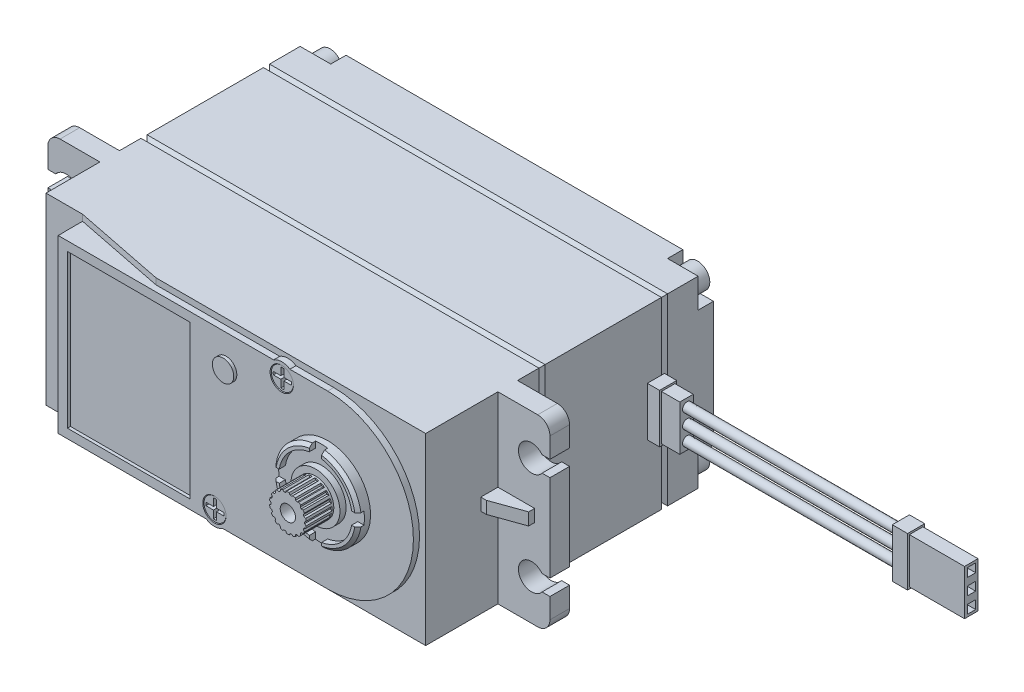
SolidWorks part; units mm, degrees
ref_plane "前视基准面" through (0, 0, 0) normal (0, 0, 1) x (1, 0, 0)
ref_plane "上视基准面" through (0, 0, 0) normal (0, 1, 0) x (1, 0, 0)
ref_plane "右视基准面" through (0, 0, 0) normal (1, 0, 0) x (0, 0, -1)
sketch "草图1" plane through (0, 0, 0) normal (0, 0, 1) x (1, 0, 0)
  line L1 (-32.5, 15) -> (32.5, 15)
  line L2 (-32.5, 15) -> (-32.5, -15)
  line L3 (-32.5, -15) -> (32.5, -15)
  line L4 (32.5, 15) -> (32.5, -15)
  dimension "D1" = 32.5
  dimension "D2" = 65
  dimension "D3" = 15
  dimension "D4" = 30
extrude "凸台-拉伸1" add sketch "草图1" along normal blind 8
chamfer "倒角1" distance 0.5 angle 45 4 edges at (0, 15, 8) (32.5, 0, 8) (0, -15, 8) (-32.5, 0, 8)
sketch "草图2" plane through (0, 0, 8) normal (0, 0, 1) x (1, 0, 0)
  line L0 (32.5, 15) -> (32.5, -15) construction
  line L1 (32.5, -15) -> (-32.5, -15) construction
  line L2 (-32.5, -15) -> (-32.5, 15) construction
  line L3 (-32.5, 15) -> (32.5, 15) construction
  line L4 (32.5, 15) -> (32.5, -15)
  line L5 (32.5, -15) -> (-32.5, -15)
  line L6 (-32.5, -15) -> (-32.5, 15)
  line L7 (-32.5, 15) -> (32.5, 15)
extrude "凸台-拉伸2" add sketch "草图2" along normal blind 20
chamfer "倒角2" distance 0.5 angle 45 4 edges at (32.5, 0, 28) (0, -15, 28) (-32.5, 0, 28) (0, 15, 28)
sketch "草图3" plane through (0, 0, 28) normal (0, 0, 1) x (1, 0, 0)
  line L0 (32.5, 15) -> (32.5, -15) construction
  line L1 (32.5, -15) -> (-32.5, -15) construction
  line L2 (-32.5, -15) -> (-32.5, 15) construction
  line L3 (-32.5, 15) -> (32.5, 15) construction
  line L4 (32.5, 15) -> (32.5, -15)
  line L5 (32.5, -15) -> (-32.5, -15)
  line L6 (-32.5, -15) -> (-32.5, 15)
  line L7 (-32.5, 15) -> (32.5, 15)
extrude "凸台-拉伸3" add sketch "草图3" along normal blind 20
chamfer "倒角3" distance 0.5 angle 45 8 edges at (-32.5, 0, 28) (0, -15, 28) (0, 15, 28) (32.5, 0, 28) (32.5, 0, 8) (0, 15, 8) (-32.5, 0, 8) (0, -15, 8)
sketch "草图4" plane through (0, 0, 48) normal (0, 0, 1) x (1, 0, 0)
  line L0 (32.5, -15) -> (32.5, 15) construction
  circle A0 centre (17.5, 0) radius 7
  dimension "D1" = 15
  dimension "D2" = 14
extrude "凸台-拉伸4" add sketch "草图4" along normal blind 2
sketch "草图5" plane through (0, 0, 50) normal (0, 0, 1) x (1, 0, 0)
  circle A0 centre (17.5, 0) radius 3
  dimension "D1" = 6
extrude "凸台-拉伸5" add sketch "草图5" along normal blind 4.5
sketch "草图6" plane through (0, 0, 54.5) normal (0, 0, 1) x (1, 0, 0)
  circle A0 centre (17.5, 0) radius 1.25
  dimension "D1" = 2.5
extrude "切除-拉伸1" cut sketch "草图6" against normal blind 5
sketch "草图7" plane through (0, 0, 50) normal (0, 0, 1) x (1, 0, 0)
  circle A0 centre (17.5, 0) radius 4
  circle A1 centre (17.5, 0) radius 6
  dimension "D1" = 12
  dimension "D2" = 8
extrude "切除-拉伸2" cut sketch "草图7" against normal blind 1
sketch "草图8" plane through (0, 0, 50) normal (0, 0, 1) x (1, 0, 0)
  line L0 (18.5, -6.9282) -> (18.5, -5.9161)
  line L1 (24.4282, -1) -> (23.4161, -1)
  line L2 (10.5718, -1) -> (11.5839, -1)
  line L3 (18.5, 6.9282) -> (18.5, 5.9161)
  line L4 (16.5, -6.9282) -> (16.5, -5.9161)
  line L5 (24.4282, 1) -> (23.4161, 1)
  line L6 (16.5, 6.9282) -> (16.5, 5.9161)
  line L7 (10.5718, 1) -> (11.5839, 1)
  line L8 (10.5, 0) -> (24.5, 0) construction
  circle A1 centre (17.5, 0) radius 7 construction
  circle A11 centre (17.5, 0) radius 7 construction
  circle A14 centre (17.5, 0) radius 6 construction
  arc A15 (11.5839, 1) -> (11.5839, -1) centre (17.5, 0) ccw
  arc A16 (10.5718, 1) -> (10.5718, -1) centre (17.5, 0) ccw
  arc A17 (18.5, 6.9282) -> (16.5, 6.9282) centre (17.5, 0) ccw
  arc A18 (18.5, 5.9161) -> (16.5, 5.9161) centre (17.5, 0) ccw
  arc A19 (24.4282, -1) -> (24.4282, 1) centre (17.5, 0) ccw
  arc A20 (23.4161, -1) -> (23.4161, 1) centre (17.5, 0) ccw
  arc A21 (16.5, -5.9161) -> (18.5, -5.9161) centre (17.5, 0) ccw
  arc A22 (16.5, -6.9282) -> (18.5, -6.9282) centre (17.5, 0) ccw
  point P12 (21.5, 7)
  point P13 (21.5, -7.2442)
  point P16 (23.5, 7)
  point P17 (23.5, -7.2442)
  point P29 (17.5, 0)
  dimension "D2" = 1
  dimension "D3" = 1
  dimension "D4" = 1
  dimension "D5" = 1
  dimension "D1" = 4
extrude "切除-拉伸3" cut sketch "草图8" against normal blind 1
chamfer "倒角4" distance 0.5 angle 45 4 edges at (22.4497, -4.9497, 50) (22.4497, 4.9497, 50) (12.5503, 4.9497, 50) (12.5503, -4.9497, 50)
sketch "草图9" plane through (0, 0, 54.5) normal (0, 0, 1) x (1, 0, 0)
  line L0 (18.1005, 2.6732) -> (18.3385, 2.8804)
  line L58 (17.15, 2.7174) -> (17.3027, 2.9935)
  line L92 (16.8995, 2.6732) -> (16.6615, 2.8804)
  line L94 (17.85, 2.7174) -> (17.6973, 2.9935)
  line L96 (18.9786, 2.3066) -> (19.2731, 2.42)
  line L98 (18.7583, 2.4338) -> (18.7092, 2.7455)
  line L100 (19.6783, 1.6618) -> (19.9938, 1.6676)
  line L102 (19.5148, 1.8567) -> (19.5753, 2.1664)
  line L104 (20.1153, 0.8166) -> (20.4138, 0.7141)
  line L106 (20.0283, 1.0556) -> (20.1911, 1.3259)
  line L108 (20.2369, -0.1272) -> (20.4823, -0.3256)
  line L110 (20.2369, 0.1272) -> (20.4823, 0.3256)
  line L112 (20.0283, -1.0556) -> (20.1911, -1.3259)
  line L114 (20.1153, -0.8166) -> (20.4138, -0.7141)
  line L116 (19.5148, -1.8567) -> (19.5753, -2.1664)
  line L118 (19.6783, -1.6618) -> (19.9938, -1.6676)
  line L120 (18.7583, -2.4338) -> (18.7092, -2.7455)
  line L122 (18.9786, -2.3066) -> (19.2731, -2.42)
  line L123 (17.85, -2.7174) -> (17.6973, -2.9935)
  line L124 (18.1005, -2.6732) -> (18.3385, -2.8804)
  line L125 (16.8995, -2.6732) -> (16.6615, -2.8804)
  line L126 (17.15, -2.7174) -> (17.3027, -2.9935)
  line L127 (16.0214, -2.3066) -> (15.7269, -2.42)
  line L128 (16.2417, -2.4338) -> (16.2908, -2.7455)
  line L129 (15.3217, -1.6618) -> (15.0062, -1.6676)
  line L130 (15.4852, -1.8567) -> (15.4247, -2.1664)
  line L131 (14.8847, -0.8166) -> (14.5862, -0.7141)
  line L132 (14.9717, -1.0556) -> (14.8089, -1.3259)
  line L133 (14.7631, 0.1272) -> (14.5177, 0.3256)
  line L134 (14.7631, -0.1272) -> (14.5177, -0.3256)
  line L135 (14.9717, 1.0556) -> (14.8089, 1.3259)
  line L136 (14.8847, 0.8166) -> (14.5862, 0.7141)
  line L137 (15.4852, 1.8567) -> (15.4247, 2.1664)
  line L138 (15.3217, 1.6618) -> (15.0062, 1.6676)
  line L139 (16.2417, 2.4338) -> (16.2908, 2.7455)
  line L140 (16.0214, 2.3066) -> (15.7269, 2.42)
  arc A53 (17.15, 2.7174) -> (16.8995, 2.6732) centre (17.5, 0) ccw
  arc A86 (18.3385, 2.8804) -> (17.6973, 2.9935) centre (17.5, 0) ccw
  circle A88 centre (17.5, 0) radius 3 construction
  arc A89 (17.3027, 2.9935) -> (16.6615, 2.8804) centre (17.5, 0) ccw
  arc A90 (18.1005, 2.6732) -> (17.85, 2.7174) centre (17.5, 0) ccw
  arc A91 (19.2731, 2.42) -> (18.7092, 2.7455) centre (17.5, 0) ccw
  arc A92 (18.9786, 2.3066) -> (18.7583, 2.4338) centre (17.5, 0) ccw
  arc A93 (19.9938, 1.6676) -> (19.5753, 2.1664) centre (17.5, 0) ccw
  arc A94 (19.6783, 1.6618) -> (19.5148, 1.8567) centre (17.5, 0) ccw
  arc A95 (20.4138, 0.7141) -> (20.1911, 1.3259) centre (17.5, 0) ccw
  arc A96 (20.1153, 0.8166) -> (20.0283, 1.0556) centre (17.5, 0) ccw
  arc A97 (20.4823, -0.3256) -> (20.4823, 0.3256) centre (17.5, 0) ccw
  arc A98 (20.2369, -0.1272) -> (20.2369, 0.1272) centre (17.5, 0) ccw
  arc A99 (20.1911, -1.3259) -> (20.4138, -0.7141) centre (17.5, 0) ccw
  arc A100 (20.0283, -1.0556) -> (20.1153, -0.8166) centre (17.5, 0) ccw
  arc A101 (19.5753, -2.1664) -> (19.9938, -1.6676) centre (17.5, 0) ccw
  arc A102 (19.5148, -1.8567) -> (19.6783, -1.6618) centre (17.5, 0) ccw
  arc A103 (18.7092, -2.7455) -> (19.2731, -2.42) centre (17.5, 0) ccw
  arc A104 (18.7583, -2.4338) -> (18.9786, -2.3066) centre (17.5, 0) ccw
  arc A105 (17.6973, -2.9935) -> (18.3385, -2.8804) centre (17.5, 0) ccw
  arc A106 (17.85, -2.7174) -> (18.1005, -2.6732) centre (17.5, 0) ccw
  arc A107 (16.6615, -2.8804) -> (17.3027, -2.9935) centre (17.5, 0) ccw
  arc A108 (16.8995, -2.6732) -> (17.15, -2.7174) centre (17.5, 0) ccw
  arc A109 (15.7269, -2.42) -> (16.2908, -2.7455) centre (17.5, 0) ccw
  arc A110 (16.0214, -2.3066) -> (16.2417, -2.4338) centre (17.5, 0) ccw
  arc A111 (15.0062, -1.6676) -> (15.4247, -2.1664) centre (17.5, 0) ccw
  arc A112 (15.3217, -1.6618) -> (15.4852, -1.8567) centre (17.5, 0) ccw
  arc A113 (14.5862, -0.7141) -> (14.8089, -1.3259) centre (17.5, 0) ccw
  arc A114 (14.8847, -0.8166) -> (14.9717, -1.0556) centre (17.5, 0) ccw
  arc A115 (14.5177, 0.3256) -> (14.5177, -0.3256) centre (17.5, 0) ccw
  arc A116 (14.7631, 0.1272) -> (14.7631, -0.1272) centre (17.5, 0) ccw
  arc A117 (14.8089, 1.3259) -> (14.5862, 0.7141) centre (17.5, 0) ccw
  arc A118 (14.9717, 1.0556) -> (14.8847, 0.8166) centre (17.5, 0) ccw
  arc A119 (15.4247, 2.1664) -> (15.0062, 1.6676) centre (17.5, 0) ccw
  arc A120 (15.4852, 1.8567) -> (15.3217, 1.6618) centre (17.5, 0) ccw
  arc A121 (16.2908, 2.7455) -> (15.7269, 2.42) centre (17.5, 0) ccw
  arc A122 (16.2417, 2.4338) -> (16.0214, 2.3066) centre (17.5, 0) ccw
  point P76 (17.5, 0)
extrude "切除-拉伸4" cut sketch "草图9" against normal blind 4.2
ref_plane "基准面1" through (0, 0, 32) normal (0, 0, -1) x (-1, 0, 0)
sketch "草图10" plane through (0, 0, 32) normal (0, 0, -1) x (-1, 0, 0)
  line L2 (41, -9.7) -> (41, -15)
  line L3 (-32.5, -15) -> (-32.5, 15) construction
  line L4 (-41, 15) -> (-41, 9.7)
  line L5 (41, 7.1) -> (41, -7.1)
  line L6 (-32.5, 15) -> (-41, 15)
  line L7 (-32.5, -15) -> (-41, -15)
  line L8 (-32.5, -15) -> (-32.5, 15)
  line L10 (-39.7125, 9.7) -> (-41, 9.7)
  line L11 (-39.7125, 7.1) -> (-41, 7.1)
  line L12 (-39.7125, -7.1) -> (-41, -7.1)
  line L13 (-39.7125, -9.7) -> (-41, -9.7)
  line L14 (-41, 7.1) -> (-41, -7.1)
  line L15 (-41, -9.7) -> (-41, -15)
  line L16 (39.7125, -9.7) -> (41, -9.7)
  line L17 (39.7125, -7.1) -> (41, -7.1)
  line L18 (39.7125, 7.1) -> (41, 7.1)
  line L19 (39.7125, 9.7) -> (41, 9.7)
  line L20 (32.5, -15) -> (32.5, 15)
  line L21 (32.5, -15) -> (41, -15)
  line L22 (32.5, 15) -> (41, 15)
  line L23 (41, 15) -> (41, 9.7)
  arc A0 (-39.7125, 7.1) -> (-39.7125, 9.7) centre (-38, 8.4) ccw
  arc A1 (-39.7125, -7.1) -> (-39.7125, -9.7) centre (-38, -8.4) cw
  arc A2 (39.7125, -7.1) -> (39.7125, -9.7) centre (38, -8.4) ccw
  arc A3 (39.7125, 7.1) -> (39.7125, 9.7) centre (38, 8.4) cw
  point P10 (-41, -23.8015)
  dimension "D4" = 4.3
extrude "凸台-拉伸6" add sketch "草图10" against normal blind 3.2
sketch "草图11" plane through (0, 0, 35.2) normal (0, 0, 1) x (1, 0, 0)
  line L2 (-38.5, -0.4932) -> (-32.5, -0.4932)
  line L3 (-38.5, 1.5068) -> (-32.5, 1.5068)
  line L4 (-32.5, 15) -> (-32.5, -15) construction
  line L5 (-32.5, 1.5068) -> (-32.5, -0.4932)
  line L6 (-38.5, 1.5068) -> (-38.5, -0.4932)
  line L8 (38.5, 1.5068) -> (38.5, -0.4932)
  line L9 (32.5, 1.5068) -> (32.5, -0.4932)
  line L10 (-32.5, 15) -> (-32.5, -15) construction
  line L11 (-38.5, 15) -> (-38.5, -15) construction
  line L12 (38.5, 1.5068) -> (32.5, 1.5068)
  line L13 (38.5, -0.4932) -> (32.5, -0.4932)
  point P4 (-41, -0.4932)
  point P5 (-31.3402, -0.4932)
  point P6 (-41, 1.5068)
  point P7 (-31.3402, 1.5068)
  dimension "D3" = 6
extrude "凸台-拉伸7" add sketch "草图11" along normal blind 2.8
sketch "草图12" plane through (0, -0.4932, 0) normal (0, -1, 0) x (1, 0, 0)
  line L0 (-38.5, 36.1787) -> (-33.4098, 38)
  line L1 (-38.5, 38) -> (-38.5, 35.2) construction
  line L2 (-33.4098, 38) -> (-38.5, 38)
  line L3 (-38.5, 38) -> (-38.5, 36.1787)
  line L6 (38.5, 38) -> (38.5, 36.1787)
  line L7 (33.4098, 38) -> (38.5, 38)
  line L8 (38.5, 36.1787) -> (33.4098, 38)
extrude "切除-拉伸5" cut sketch "草图12" against normal blind 2.8
sketch "草图15" plane through (0, 0, 48) normal (0, 0, 1) x (1, 0, 0)
  line L0 (17.5, 14) -> (-26.5, 14)
  line L1 (17.5, -14) -> (-26.5, -14)
  line L2 (-26.5, 14) -> (-26.5, -14)
  line L3 (-32.5, 15) -> (-32.5, -15) construction
  line L4 (-32.5, 15) -> (32.5, 15)
  line L5 (32.5, 15) -> (32.5, -15)
  line L6 (32.5, -15) -> (-32.5, -15)
  line L7 (-32.5, -15) -> (-32.5, 15)
  arc A1 (17.5, -14) -> (17.5, 14) centre (17.5, 0) ccw
  dimension "D1" = 28
  dimension "D2" = 6
extrude "切除-拉伸6" cut sketch "草图15" against normal blind 1
sketch "草图16" plane through (0, 0, 47) normal (0, 0, 1) x (1, 0, 0)
  line L0 (-32.5, -15) -> (32.5, -15) construction
  line L1 (-32.5, 15) -> (-26.5251, 15)
  line L2 (-32.5, 15) -> (-32.5, -15)
  line L3 (-32.5, -15) -> (-26.5251, -15)
  line L4 (-26.5251, 15) -> (-26.5251, -15)
extrude "切除-拉伸7" cut sketch "草图16" against normal blind 3
sketch "草图17" plane through (0, -15, 0) normal (0, -1, 0) x (1, 0, 0)
  line L0 (-26.5251, 44) -> (-11.5251, 47)
  line L1 (-26.5251, 47) -> (32.5, 47) construction
  line L2 (-11.5251, 47) -> (-26.5251, 47)
  line L3 (-26.5251, 47) -> (-26.5251, 44)
  dimension "D1" = 15
extrude "切除-拉伸8" cut sketch "草图17" against normal blind 1
mirror "镜向1" about plane through (0, 0, 0) normal (0, 1, 0) of "切除-拉伸8"
sketch "草图18" plane through (0, 0, 48) normal (0, 0, 1) x (1, 0, 0)
  line L0 (-26.5, 14) -> (-26.5, -14) construction
  line L1 (-25, 12.5) -> (-5, 12.5)
  line L2 (-25, 12.5) -> (-25, -12.5)
  line L3 (-25, -12.5) -> (-5, -12.5)
  line L4 (-5, 12.5) -> (-5, -12.5)
  line L5 (-26.5251, 14) -> (-11.5251, 14) construction
  line L6 (-26.5, -14) -> (17.5, -14) construction
  dimension "D1" = 20
  dimension "D2" = 1.5
  dimension "D3" = 1.5
  dimension "D4" = 1.5
extrude "切除-拉伸9" cut sketch "草图18" against normal blind 0.5
sketch "草图19" plane through (0, 0, 48) normal (0, 0, 1) x (1, 0, 0)
  circle A0 centre (0.9122, 8.8935) radius 1.75
  dimension "D1" = 3.5
extrude "凸台-拉伸8" add sketch "草图19" along normal blind 0.5
sketch "草图21" plane through (0, 0, 47) normal (0, 0, 1) x (1, 0, 0)
  line L0 (32.5, 15) -> (-11.5251, 15) construction
  line L1 (-11.5251, -15) -> (32.5, -15) construction
  circle A0 centre (10, 12) radius 2.4
  circle A1 centre (-1, -12) radius 2.4
  dimension "D1" = 4.8
  dimension "D2" = 3
  dimension "D3" = 10
  dimension "D4" = 4.8
  dimension "D5" = 3
  dimension "D6" = 1
extrude "凸台-拉伸9" add sketch "草图21" along normal blind 1
sketch "草图22" plane through (0, 0, 48) normal (0, 0, 1) x (1, 0, 0)
  circle A0 centre (-1, -12) radius 1.9
  circle A1 centre (10, 12) radius 1.9
  dimension "D1" = 3.8
  dimension "D2" = 3.8
extrude "切除-拉伸11" cut sketch "草图22" against normal blind 1.4
sketch "草图23" plane through (0, 0, 46.6) normal (0, 0, 1) x (1, 0, 0)
  line L6 (10.25, 11.75) -> (10.25, 10.521)
  line L7 (10.25, 12.25) -> (11.479, 12.25)
  line L9 (9.75, 11.75) -> (9.75, 10.521)
  line L11 (10.25, 11.75) -> (11.479, 11.75)
  line L14 (-1.25, -12.25) -> (-1.25, -13.479)
  line L15 (-0.75, -11.75) -> (0.479, -11.75)
  line L16 (9.75, 13.479) -> (9.75, 12.25)
  line L17 (10.25, 13.479) -> (10.25, 12.25)
  line L18 (8.521, 12.25) -> (9.75, 12.25)
  line L19 (8.521, 11.75) -> (9.75, 11.75)
  line L21 (-0.75, -12.25) -> (-0.75, -13.479)
  line L23 (-0.75, -12.25) -> (0.479, -12.25)
  line L27 (-0.75, -10.521) -> (-0.75, -11.75)
  line L28 (-1.25, -10.521) -> (-1.25, -11.75)
  line L29 (-2.479, -11.75) -> (-1.25, -11.75)
  line L30 (-2.479, -12.25) -> (-1.25, -12.25)
  circle A0 centre (10, 12) radius 1.8
  arc A1 (10.25, 13.479) -> (9.75, 13.479) centre (10, 12) ccw
  arc A2 (8.521, 12.25) -> (8.521, 11.75) centre (10, 12) ccw
  arc A3 (9.75, 10.521) -> (10.25, 10.521) centre (10, 12) ccw
  arc A4 (11.479, 11.75) -> (11.479, 12.25) centre (10, 12) ccw
  circle A5 centre (-1, -12) radius 1.8
  arc A6 (0.479, -12.25) -> (0.479, -11.75) centre (-1, -12) ccw
  arc A9 (-0.75, -10.521) -> (-1.25, -10.521) centre (-1, -12) ccw
  arc A10 (-2.479, -11.75) -> (-2.479, -12.25) centre (-1, -12) ccw
  arc A11 (-1.25, -13.479) -> (-0.75, -13.479) centre (-1, -12) ccw
  point P8 (8.2, 11.75)
  point P9 (12.0905, 11.75)
  point P10 (9.75, 13.8)
  point P11 (9.75, 9.8425)
  point P12 (8.2, 12.25)
  point P13 (12.0905, 12.25)
  point P14 (10.25, 13.8)
  point P15 (10.25, 9.8425)
  point P39 (-2.8, -12.25)
  point P40 (1.2543, -12.25)
  point P41 (-1.25, -10.1)
  point P42 (-1.25, -14.0125)
  point P43 (-2.8, -11.75)
  point P44 (1.2543, -11.75)
  point P45 (-0.75, -10.1)
  point P46 (-0.75, -14.0125)
  dimension "D1" = 3.6
  dimension "D2" = 3
  dimension "D3" = 3.6
  dimension "D4" = 3
extrude "凸台-拉伸10" add sketch "草图23" along normal blind 1.3
sketch "草图24" plane through (0, 0, 0) normal (0, 0, -1) x (-1, 0, 0)
  line L4 (-27.5, 12.7029) -> (-27.5, 15)
  line L5 (-30, 10.2029) -> (-32.5, 10.2029)
  line L6 (-32.5, 10.2029) -> (-32.5, 15)
  line L9 (-27.5, 15) -> (-32.5, 15)
  line L11 (-27.5, -15) -> (-32.5, -15)
  line L12 (-32.5, -10.2029) -> (-32.5, -15)
  line L13 (-30, -10.2029) -> (-32.5, -10.2029)
  line L14 (-27.5, -12.7029) -> (-27.5, -15)
  line L15 (27.5, -12.7029) -> (27.5, -15)
  line L16 (30, -10.2029) -> (32.5, -10.2029)
  line L17 (32.5, -10.2029) -> (32.5, -15)
  line L18 (27.5, -15) -> (32.5, -15)
  line L19 (27.5, 15) -> (32.5, 15)
  line L20 (32.5, 10.2029) -> (32.5, 15)
  line L21 (30, 10.2029) -> (32.5, 10.2029)
  line L22 (27.5, 12.7029) -> (27.5, 15)
  arc A0 (-30, 10.2029) -> (-27.5, 12.7029) centre (-30, 12.7029) ccw
  arc A1 (-30, -10.2029) -> (-27.5, -12.7029) centre (-30, -12.7029) cw
  arc A2 (30, -10.2029) -> (27.5, -12.7029) centre (30, -12.7029) ccw
  arc A3 (30, 10.2029) -> (27.5, 12.7029) centre (30, 12.7029) cw
  dimension "D1" = 5
extrude "切除-拉伸12" cut sketch "草图24" against normal blind 2.5
sketch "草图25" plane through (0, 0, 2.5) normal (0, 0, -1) x (-1, 0, 0)
  line L0 (-29.7, 13.0029) -> (-28.2252, 13.0029)
  line L1 (-30.3, 12.4029) -> (-30.3, 10.928)
  line L2 (-29.7, 12.4029) -> (-29.7, 10.928)
  line L3 (-29.7, 12.4029) -> (-28.2252, 12.4029)
  line L6 (-29.7, 14.4777) -> (-29.7, 13.0029)
  line L7 (-30.3, 14.4777) -> (-30.3, 13.0029)
  line L8 (-31.7748, -13.0029) -> (-30.3, -13.0029)
  line L9 (-31.7748, -12.4029) -> (-30.3, -12.4029)
  line L10 (-30.3, -14.4777) -> (-30.3, -13.0029)
  line L11 (-31.7748, 12.4029) -> (-30.3, 12.4029)
  line L12 (-29.7, -14.4777) -> (-29.7, -13.0029)
  line L13 (-31.7748, 13.0029) -> (-30.3, 13.0029)
  line L14 (-29.7, -12.4029) -> (-28.2252, -12.4029)
  line L15 (-29.7, -12.4029) -> (-29.7, -10.928)
  line L16 (-30.3, -12.4029) -> (-30.3, -10.928)
  line L17 (-29.7, -13.0029) -> (-28.2252, -13.0029)
  line L20 (29.7, -13.0029) -> (28.2252, -13.0029)
  line L21 (30.3, -12.4029) -> (30.3, -10.928)
  line L22 (29.7, -12.4029) -> (29.7, -10.928)
  line L23 (29.7, -12.4029) -> (28.2252, -12.4029)
  line L24 (29.7, -14.4777) -> (29.7, -13.0029)
  line L25 (30.3, -14.4777) -> (30.3, -13.0029)
  line L26 (31.7748, -12.4029) -> (30.3, -12.4029)
  line L27 (31.7748, -13.0029) -> (30.3, -13.0029)
  line L28 (31.7748, 13.0029) -> (30.3, 13.0029)
  line L29 (31.7748, 12.4029) -> (30.3, 12.4029)
  line L30 (30.3, 14.4777) -> (30.3, 13.0029)
  line L31 (29.7, 14.4777) -> (29.7, 13.0029)
  line L32 (29.7, 12.4029) -> (28.2252, 12.4029)
  line L33 (29.7, 12.4029) -> (29.7, 10.928)
  line L34 (30.3, 12.4029) -> (30.3, 10.928)
  line L35 (29.7, 13.0029) -> (28.2252, 13.0029)
  circle A0 centre (-30, 12.7029) radius 2
  arc A1 (-29.7, 14.4777) -> (-30.3, 14.4777) centre (-30, 12.7029) ccw
  arc A2 (-31.7748, 13.0029) -> (-31.7748, 12.4029) centre (-30, 12.7029) ccw
  arc A3 (-30.3, 10.928) -> (-29.7, 10.928) centre (-30, 12.7029) ccw
  arc A4 (-28.2252, 12.4029) -> (-28.2252, 13.0029) centre (-30, 12.7029) ccw
  arc A5 (-28.2252, -12.4029) -> (-28.2252, -13.0029) centre (-30, -12.7029) cw
  arc A6 (-30.3, -10.928) -> (-29.7, -10.928) centre (-30, -12.7029) cw
  arc A7 (-31.7748, -13.0029) -> (-31.7748, -12.4029) centre (-30, -12.7029) cw
  arc A8 (-29.7, -14.4777) -> (-30.3, -14.4777) centre (-30, -12.7029) cw
  circle A9 centre (-30, -12.7029) radius 2
  circle A10 centre (30, -12.7029) radius 2
  arc A11 (29.7, -14.4777) -> (30.3, -14.4777) centre (30, -12.7029) ccw
  arc A12 (31.7748, -13.0029) -> (31.7748, -12.4029) centre (30, -12.7029) ccw
  arc A13 (30.3, -10.928) -> (29.7, -10.928) centre (30, -12.7029) ccw
  arc A14 (28.2252, -12.4029) -> (28.2252, -13.0029) centre (30, -12.7029) ccw
  arc A15 (28.2252, 12.4029) -> (28.2252, 13.0029) centre (30, 12.7029) cw
  arc A16 (30.3, 10.928) -> (29.7, 10.928) centre (30, 12.7029) cw
  arc A17 (31.7748, 13.0029) -> (31.7748, 12.4029) centre (30, 12.7029) cw
  arc A18 (29.7, 14.4777) -> (30.3, 14.4777) centre (30, 12.7029) cw
  circle A19 centre (30, 12.7029) radius 2
  point P8 (-32, 12.4029)
  point P9 (-27.7989, 12.4029)
  point P10 (-30.3, 14.7029)
  point P11 (-30.3, 10.7029)
  point P12 (-32, 13.0029)
  point P13 (-27.7989, 13.0029)
  point P14 (-29.7, 14.7029)
  point P15 (-29.7, 10.7029)
  dimension "D1" = 4
  dimension "D2" = 3.6
extrude "凸台-拉伸11" add sketch "草图25" along normal blind 2.4
sketch "草图26" plane through (32.5, 0, 0) normal (1, 0, 0) x (0, 0, -1)
  line L0 (-8, -14.5) -> (-8, 14.5) construction
  line L2 (-10.8, 4) -> (-8, 4)
  line L3 (-10.8, 4) -> (-10.8, -4)
  line L4 (-10.8, -4) -> (-8, -4)
  line L5 (-8, 4) -> (-8, -4)
  dimension "D1" = 2.8
  dimension "D2" = 8
  dimension "D4" = 0
extrude "凸台-拉伸12" add sketch "草图26" along normal blind 2
sketch "草图27" plane through (34.5, 0, 0) normal (1, 0, 0) x (0, 0, -1)
  line L16 (-10.5, 3.7) -> (-10.5, -3.7)
  line L17 (-10.5, -3.7) -> (-8.3, -3.7)
  line L18 (-8.3, -3.7) -> (-8.3, 3.7)
  line L19 (-8.3, 3.7) -> (-10.5, 3.7)
  line L20 (-10.5, 3.7) -> (-10.5, -3.7)
  line L21 (-10.5, -3.7) -> (-8.3, -3.7)
  line L22 (-8.3, -3.7) -> (-8.3, 3.7)
  line L23 (-8.3, 3.7) -> (-10.5, 3.7)
  dimension "D2" = 0.3
extrude "凸台-拉伸13" add sketch "草图27" along normal blind 3
sketch "草图28" plane through (37.5, 0, 0) normal (1, 0, 0) x (0, 0, -1)
  line L0 (-8.3, 3.7) -> (-10.5, 3.7) construction
  line L1 (-8.3, -3.7) -> (-8.3, 3.7) construction
  circle A0 centre (-9.3, 0) radius 0.75
  circle A1 centre (-9.3, 2.4) radius 0.75
  circle A2 centre (-9.3, -2.4) radius 0.75
  dimension "D1" = 1.5
  dimension "D2" = 1.5
  dimension "D3" = 1.5
  dimension "D4" = 1.3
  dimension "D5" = 2.4
  dimension "D6" = 2.4
  dimension "D7" = 1
extrude "凸台-拉伸14" add sketch "草图28" along normal blind 35
sketch "草图29" plane through (72.5, 0, 0) normal (1, 0, 0) x (0, 0, -1)
  line L0 (-8, -14.5) -> (-8, 14.5) construction
  line L1 (-10.8, 4) -> (-8, 4)
  line L2 (-10.8, 4) -> (-10.8, -4)
  line L3 (-10.8, -4) -> (-8, -4)
  line L4 (-8, 4) -> (-8, -4)
  line L5 (-10.8, -4) -> (-8, -4) construction
extrude "凸台-拉伸15" add sketch "草图29" along normal blind 2.5
sketch "草图30" plane through (75, 0, 0) normal (1, 0, 0) x (0, 0, -1)
  line L5 (-10.0126, 3.3) -> (-8.6871, 3.3)
  line L6 (-10.0126, 3.3) -> (-10.0126, 1.9)
  line L7 (-10.0126, 1.9) -> (-8.6871, 1.9)
  line L16 (-10.5, 3.7) -> (-10.5, -3.7)
  line L17 (-10.5, -3.7) -> (-8.3, -3.7)
  line L18 (-8.3, -3.7) -> (-8.3, 3.7)
  line L19 (-8.3, 3.7) -> (-10.5, 3.7)
  line L20 (-10.5, 3.7) -> (-10.5, -3.7)
  line L21 (-10.5, -3.7) -> (-8.3, -3.7)
  line L22 (-8.3, -3.7) -> (-8.3, 3.7)
  line L23 (-8.3, 3.7) -> (-10.5, 3.7)
  line L24 (-8.6871, 3.3) -> (-8.6871, 1.9)
  line L25 (-10.0126, 0.7) -> (-8.6871, 0.7)
  line L26 (-10.0126, 0.7) -> (-10.0126, -0.7)
  line L27 (-10.0126, -0.7) -> (-8.6871, -0.7)
  line L28 (-8.6871, 0.7) -> (-8.6871, -0.7)
  line L29 (-10.0126, -1.9) -> (-8.6871, -1.9)
  line L30 (-10.0126, -1.9) -> (-10.0126, -3.3)
  line L31 (-10.0126, -3.3) -> (-8.6871, -3.3)
  line L32 (-8.6871, -1.9) -> (-8.6871, -3.3)
  point P16 (-9.4, 3.7)
  dimension "D1" = 1.4
  dimension "D3" = 1.4
  dimension "D4" = 1.4
  dimension "D5" = 0.4
  dimension "D6" = 1.2
  dimension "D7" = 1.2
  dimension "D2" = 0.3
extrude "凸台-拉伸16" add sketch "草图30" along normal blind 9
fillet "圆角1" radius 2 4 edges at (41, 15, 33.6) (41, -15, 33.6) (-41, 15, 33.6) (-41, -15, 33.6)
